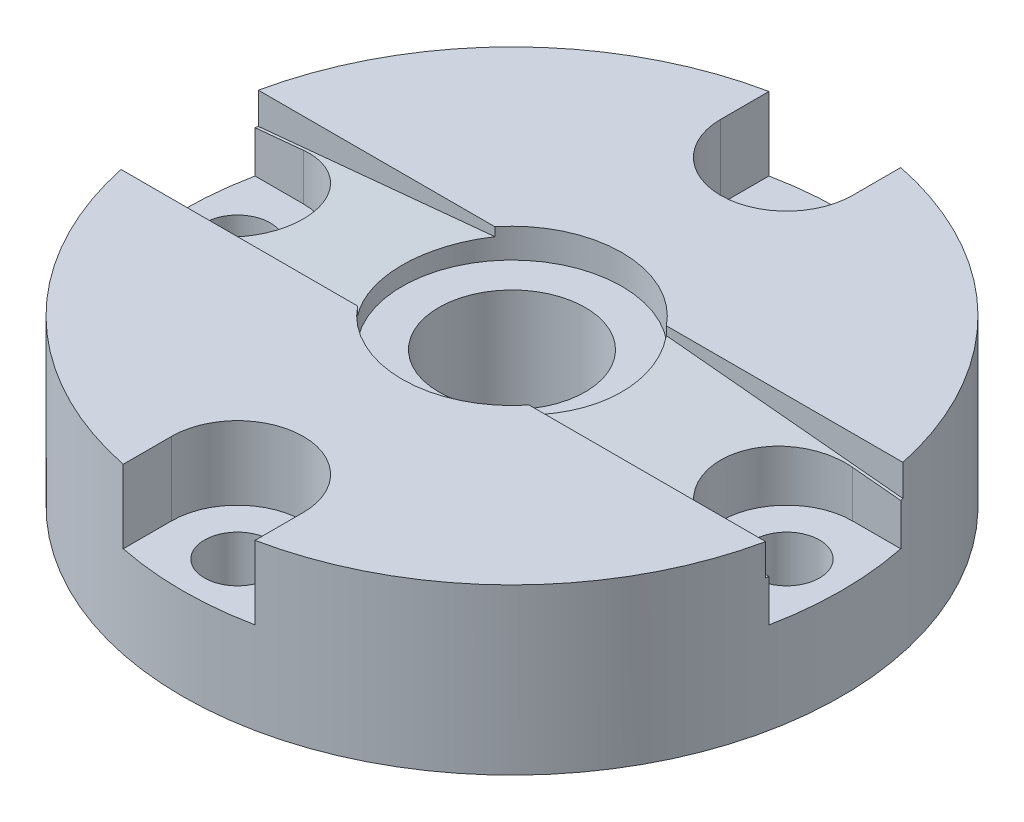
SolidWorks part; units mm, degrees
ref_plane "Plan de face" through (0, 0, 0) normal (0, 0, 1) x (1, 0, 0)
ref_plane "Plan de dessus" through (0, 0, 0) normal (0, 1, 0) x (1, 0, 0)
ref_plane "Plan de droite" through (0, 0, 0) normal (1, 0, 0) x (0, 0, -1)
sketch "Esquisse1" plane through (0, 0, 0) normal (0, 1, 0) x (1, 0, 0)
  circle A0 centre (0, 0) radius 90
  dimension "D1" = 180
extrude "Boss.-Extru.1" add sketch "Esquisse1" along normal blind 45 contours A0
sketch "Esquisse2" plane through (0, 45, 0) normal (0, 1, 0) x (1, 0, 0)
  line L0 (75, 0) -> (115, 0) construction
  line L1 (75, 18) -> (115, 18)
  line L2 (75, -18) -> (115, -18)
  arc A0 (75, 18) -> (75, -18) centre (75, 0) ccw
  arc A1 (115, -18) -> (115, 18) centre (115, 0) ccw
  circle A2 centre (75, 0) radius 9
  point P4 (95, 0)
  dimension "D4" = 18
  dimension "D1" = 36
  dimension "D2" = 75
  dimension "D3" = 40
extrude "Enlèv. mat.-Extru.1" cut sketch "Esquisse2" against normal blind 45 contours A2
extrude "Enlèv. mat.-Extru.2" cut sketch "Esquisse2<3>" against normal blind 20
sketch "Esquisse2<3>" plane through (0, 45, 0) normal (0, 1, 0) x (1, 0, 0) same geometry as "Esquisse2"
sketch "Esquisse3" plane through (0, 0, 0) normal (0, 0, 1) x (1, 0, 0)
  line L6 (-0.9092, 45) -> (101.8708, 35.1034)
  line L7 (88.1816, 45) -> (-90, 45) construction
  line L8 (101.8708, 35.1034) -> (101.8708, 45)
  line L9 (101.8708, 45) -> (-0.9092, 45)
  dimension "D1" = 5.5
  dimension "D2" = 102.78
extrude "Enlèv. mat.-Extru.3" cut sketch "Esquisse3" against normal mid plane 37.5
mirror "Symétrie1" about plane through (0, 0, 0) normal (1, 0, 0) of "Enlèv. mat.-Extru.3"
pattern_circular "Répétition circulaire2" count 4 every 90 about axis through (0, 0, 0) along (0, 1, 0) of "Enlèv. mat.-Extru.1", "Enlèv. mat.-Extru.2"
sketch "Esquisse4" plane through (0, 45, 0) normal (0, 1, 0) x (1, 0, 0)
  circle A0 centre (0, 0) radius 20
  circle A1 centre (0, 0) radius 30
  dimension "D1" = 40
  dimension "D2" = 60
extrude "Enlèv. mat.-Extru.4" cut sketch "Esquisse4" against normal mid plane 16 contours A1
extrude "Enlèv. mat.-Extru.5" cut sketch "Esquisse4<3>" against normal through all contours A0
sketch "Esquisse4<3>" plane through (0, 45, 0) normal (0, 1, 0) x (1, 0, 0) same geometry as "Esquisse4"
